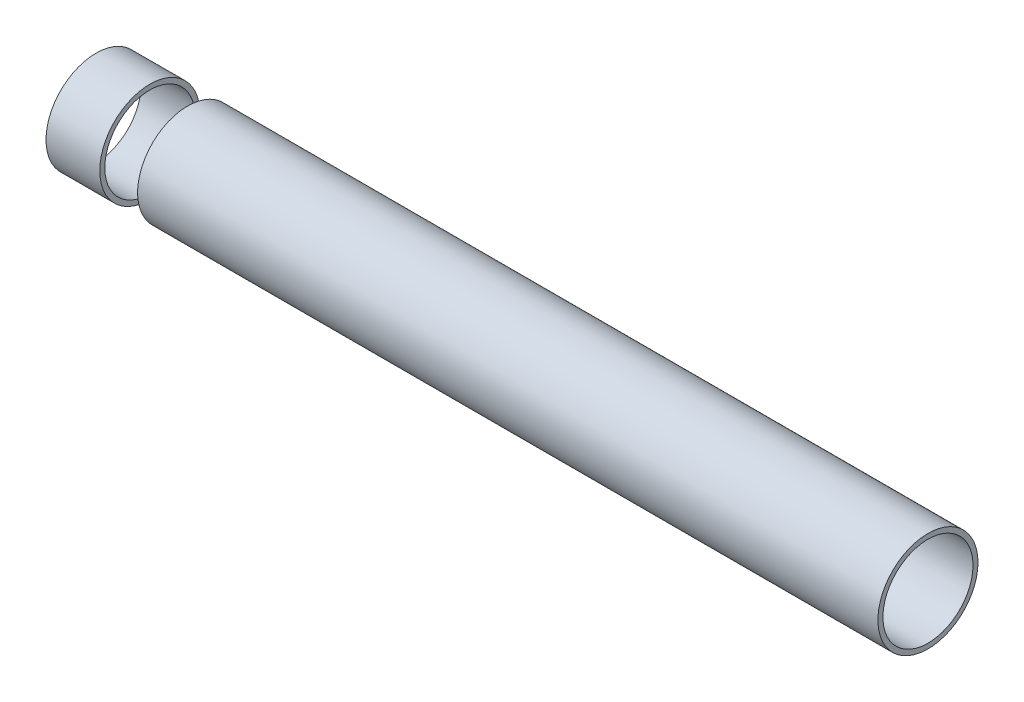
SolidWorks part; units mm, degrees
material "PC High Viscosity"
ref_plane "Front Plane" through (0, 0, 0) normal (0, 0, 1) x (1, 0, 0)
ref_plane "Top Plane" through (0, 0, 0) normal (0, 1, 0) x (1, 0, 0)
ref_plane "Right Plane" through (0, 0, 0) normal (1, 0, 0) x (0, 0, -1)
sketch "Sketch1" plane through (0, 0, 0) normal (1, 0, 0) x (0, 0, -1)
  circle A0 centre (0, 0) radius 15.875
  dimension "D1" = 31.75
extrude "Extrude-Thin1" add sketch "Sketch1" along normal mid plane 263.9115 thin thin type one direction reverse wall 1.5875
sketch "Sketch2" plane through (0, 0, 0) normal (0, 1, 0) x (1, 0, 0)
  line L0 (131.9557, 15.875) -> (-131.9557, 15.875) construction
  line L1 (-102.8953, 15.875) -> (-114.8953, 15.875)
  line L2 (-102.8953, 15.875) -> (-102.8953, -15.875)
  line L3 (-102.8953, -15.875) -> (-114.8953, -15.875)
  line L4 (-114.8953, 15.875) -> (-114.8953, -15.875)
  line L5 (-131.9557, -15.875) -> (131.9557, -15.875) construction
  line L6 (-131.9557, 14.2875) -> (-131.9557, -14.2875) construction
  point P10 (-114.2547, 15.875)
  dimension "D1" = 29.0604
  dimension "D2" = 12
extrude "Cut-Extrude1" cut sketch "Sketch2" against normal through all both and the other way through all
equation "\"D2@Sketch2\"=12mm"
